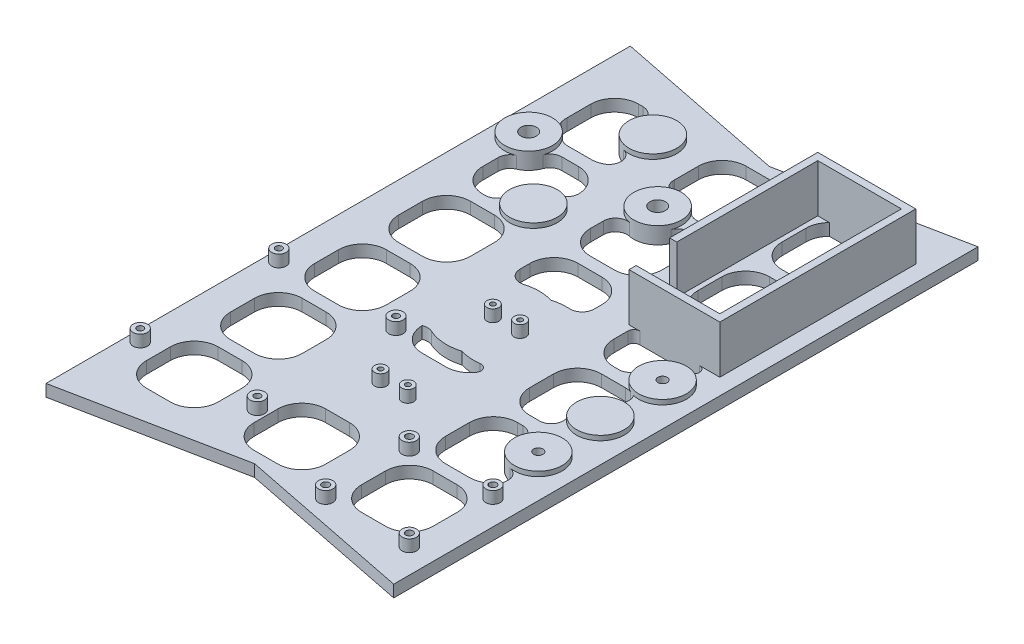
SolidWorks part; units mm, degrees
material "ABS"
ref_plane "Front Plane" through (0, 0, 0) normal (0, 0, 1) x (1, 0, 0)
ref_plane "Top Plane" through (0, 0, 0) normal (0, 1, 0) x (1, 0, 0)
ref_plane "Right Plane" through (0, 0, 0) normal (1, 0, 0) x (0, 0, -1)
ref_axis "X" through (-88.99, 0, 0) along (1, 0, 0)
ref_axis "Y" through (0, 55, 0) along (0, -1, 0)
ref_axis "Z" through (0, 0, -88.99) along (0, 0, 1)
sketch "Sketch1" plane through (0, 0, 0) normal (0, 1, 0) x (1, 0, 0)
  line L0 (-75, 125) -> (0, 110) construction
  line L1 (-75, 125) -> (75, 125) construction
  line L2 (-75, 125) -> (-75, -125) construction
  line L3 (-75, -125) -> (75, -125) construction
  line L4 (75, 125) -> (75, -125) construction
  line L5 (-75, 125) -> (75, -125) construction
  line L6 (-75, -125) -> (75, 125) construction
  line L7 (0, 110) -> (75, 125) construction
  line L8 (-75, 0) -> (75, 0) construction
  line L9 (-75, -125) -> (0, -110) construction
  line L10 (0, -110) -> (75, -125) construction
  line L11 (-73, 122.5604) -> (-73, -122.5604)
  line L12 (-73, -122.5604) -> (0, -107.9604)
  line L13 (0, -107.9604) -> (73, -122.5604)
  line L14 (73, 122.5604) -> (73, -122.5604)
  line L15 (0, 107.9604) -> (73, 122.5604)
  line L16 (-73, 122.5604) -> (0, 107.9604)
  point P0 (0, 0)
  dimension "D1" = 250
  dimension "D2" = 150
  dimension "D3" = 15
  dimension "D4" = 2
extrude "Boss-Extrude1" add sketch "Sketch1" along normal blind 5
sketch "Sketch2" plane through (0, 5, 0) normal (0, 1, 0) x (1, 0, 0)
  line L0 (-73, 122.5604) -> (-73, -122.5604) construction
  line L1 (-50, -102.9604) -> (-40, -102.9604)
  line L2 (-60, -92.9604) -> (-60, -82.9604)
  line L3 (-50, -72.9604) -> (-40, -72.9604)
  line L4 (-30, -92.9604) -> (-30, -82.9604)
  line L5 (-15, -92.9604) -> (-15, -82.9604)
  line L6 (-5, -102.9604) -> (5, -102.9604)
  line L7 (15, -92.9604) -> (15, -82.9604)
  line L8 (-5, -72.9604) -> (5, -72.9604)
  line L9 (30, -92.9604) -> (30, -82.9604)
  line L10 (40, -102.9604) -> (50, -102.9604)
  line L11 (60, -92.9604) -> (60, -82.9604)
  line L12 (40, -72.9604) -> (50, -72.9604)
  line L73 (-60, -57.7762) -> (-60, -47.7762)
  line L74 (-50, -67.7762) -> (-40, -67.7762)
  line L75 (-30, -57.7762) -> (-30, -47.7762)
  line L76 (-50, -37.7762) -> (-40, -37.7762)
  line L77 (-15, -57.7762) -> (-15, -47.7762)
  line L78 (-5, -37.7762) -> (5, -37.7762)
  line L79 (15, -57.7762) -> (15, -47.7762)
  line L80 (-5, -67.7762) -> (5, -67.7762)
  line L81 (30, -57.7762) -> (30, -47.7762)
  line L82 (40, -37.7762) -> (50, -37.7762)
  line L83 (60, -57.7762) -> (60, -47.7762)
  line L84 (40, -67.7762) -> (50, -67.7762)
  line L85 (-60, -22.5921) -> (-60, -12.5921)
  line L86 (-50, -32.5921) -> (-40, -32.5921)
  line L87 (-30, -22.5921) -> (-30, -12.5921)
  line L88 (-50, -2.5921) -> (-40, -2.5921)
  line L89 (-15, -22.5921) -> (-15, -12.5921)
  line L90 (-5, -2.5921) -> (5, -2.5921)
  line L91 (15, -22.5921) -> (15, -12.5921)
  line L92 (-5, -32.5921) -> (5, -32.5921)
  line L93 (30, -22.5921) -> (30, -12.5921)
  line L94 (40, -2.5921) -> (50, -2.5921)
  line L95 (60, -22.5921) -> (60, -12.5921)
  line L96 (40, -32.5921) -> (50, -32.5921)
  line L97 (-60, 12.5921) -> (-60, 22.5921)
  line L98 (-50, 2.5921) -> (-40, 2.5921)
  line L99 (-30, 12.5921) -> (-30, 22.5921)
  line L100 (-50, 32.5921) -> (-40, 32.5921)
  line L101 (-15, 12.5921) -> (-15, 22.5921)
  line L102 (-5, 32.5921) -> (5, 32.5921)
  line L103 (15, 12.5921) -> (15, 22.5921)
  line L104 (-5, 2.5921) -> (5, 2.5921)
  line L105 (30, 12.5921) -> (30, 22.5921)
  line L106 (40, 32.5921) -> (50, 32.5921)
  line L107 (60, 12.5921) -> (60, 22.5921)
  line L108 (40, 2.5921) -> (50, 2.5921)
  line L109 (-60, 47.7762) -> (-60, 57.7762)
  line L110 (-50, 37.7762) -> (-40, 37.7762)
  line L111 (-30, 47.7762) -> (-30, 57.7762)
  line L112 (-50, 67.7762) -> (-40, 67.7762)
  line L113 (-15, 47.7762) -> (-15, 57.7762)
  line L114 (-5, 67.7762) -> (5, 67.7762)
  line L115 (15, 47.7762) -> (15, 57.7762)
  line L116 (-5, 37.7762) -> (5, 37.7762)
  line L117 (30, 47.7762) -> (30, 57.7762)
  line L118 (40, 67.7762) -> (50, 67.7762)
  line L119 (60, 47.7762) -> (60, 57.7762)
  line L120 (40, 37.7762) -> (50, 37.7762)
  line L121 (-60, 82.9604) -> (-60, 92.9604)
  line L122 (-50, 72.9604) -> (-40, 72.9604)
  line L123 (-30, 82.9604) -> (-30, 92.9604)
  line L124 (-50, 102.9604) -> (-40, 102.9604)
  line L125 (-15, 82.9604) -> (-15, 92.9604)
  line L126 (-5, 102.9604) -> (5, 102.9604)
  line L127 (15, 82.9604) -> (15, 92.9604)
  line L128 (-5, 72.9604) -> (5, 72.9604)
  line L129 (30, 82.9604) -> (30, 92.9604)
  line L130 (40, 102.9604) -> (50, 102.9604)
  line L131 (60, 82.9604) -> (60, 92.9604)
  line L132 (40, 72.9604) -> (50, 72.9604)
  arc A0 (-60, -92.9604) -> (-50, -102.9604) centre (-50, -92.9604) ccw
  arc A1 (-40, -102.9604) -> (-30, -92.9604) centre (-40, -92.9604) ccw
  arc A2 (-30, -82.9604) -> (-40, -72.9604) centre (-40, -82.9604) ccw
  arc A3 (-50, -72.9604) -> (-60, -82.9604) centre (-50, -82.9604) ccw
  arc A4 (60, -82.9604) -> (50, -72.9604) centre (50, -82.9604) ccw
  arc A5 (50, -102.9604) -> (60, -92.9604) centre (50, -92.9604) ccw
  arc A6 (40, -102.9604) -> (30, -92.9604) centre (40, -92.9604) cw
  arc A7 (30, -82.9604) -> (40, -72.9604) centre (40, -82.9604) cw
  arc A8 (-15, -82.9604) -> (-5, -72.9604) centre (-5, -82.9604) cw
  arc A9 (-15, -92.9604) -> (-5, -102.9604) centre (-5, -92.9604) ccw
  arc A10 (15, -92.9604) -> (5, -102.9604) centre (5, -92.9604) cw
  arc A11 (15, -82.9604) -> (5, -72.9604) centre (5, -82.9604) ccw
  arc A12 (-50, -37.7762) -> (-60, -47.7762) centre (-50, -47.7762) ccw
  arc A13 (-60, -57.7762) -> (-50, -67.7762) centre (-50, -57.7762) ccw
  arc A14 (-40, -67.7762) -> (-30, -57.7762) centre (-40, -57.7762) ccw
  arc A15 (-30, -47.7762) -> (-40, -37.7762) centre (-40, -47.7762) ccw
  arc A16 (-15, -57.7762) -> (-5, -67.7762) centre (-5, -57.7762) ccw
  arc A17 (-15, -47.7762) -> (-5, -37.7762) centre (-5, -47.7762) cw
  arc A18 (15, -47.7762) -> (5, -37.7762) centre (5, -47.7762) ccw
  arc A19 (15, -57.7762) -> (5, -67.7762) centre (5, -57.7762) cw
  arc A20 (30, -47.7762) -> (40, -37.7762) centre (40, -47.7762) cw
  arc A21 (40, -67.7762) -> (30, -57.7762) centre (40, -57.7762) cw
  arc A22 (60, -47.7762) -> (50, -37.7762) centre (50, -47.7762) ccw
  arc A23 (50, -67.7762) -> (60, -57.7762) centre (50, -57.7762) ccw
  arc A24 (-50, -2.5921) -> (-60, -12.5921) centre (-50, -12.5921) ccw
  arc A25 (-60, -22.5921) -> (-50, -32.5921) centre (-50, -22.5921) ccw
  arc A26 (-40, -32.5921) -> (-30, -22.5921) centre (-40, -22.5921) ccw
  arc A27 (-30, -12.5921) -> (-40, -2.5921) centre (-40, -12.5921) ccw
  arc A28 (-15, -22.5921) -> (-5, -32.5921) centre (-5, -22.5921) ccw
  arc A29 (-15, -12.5921) -> (-5, -2.5921) centre (-5, -12.5921) cw
  arc A30 (15, -12.5921) -> (5, -2.5921) centre (5, -12.5921) ccw
  arc A31 (15, -22.5921) -> (5, -32.5921) centre (5, -22.5921) cw
  arc A32 (30, -12.5921) -> (40, -2.5921) centre (40, -12.5921) cw
  arc A33 (40, -32.5921) -> (30, -22.5921) centre (40, -22.5921) cw
  arc A34 (60, -12.5921) -> (50, -2.5921) centre (50, -12.5921) ccw
  arc A35 (50, -32.5921) -> (60, -22.5921) centre (50, -22.5921) ccw
  arc A36 (-50, 32.5921) -> (-60, 22.5921) centre (-50, 22.5921) ccw
  arc A37 (-60, 12.5921) -> (-50, 2.5921) centre (-50, 12.5921) ccw
  arc A38 (-40, 2.5921) -> (-30, 12.5921) centre (-40, 12.5921) ccw
  arc A39 (-30, 22.5921) -> (-40, 32.5921) centre (-40, 22.5921) ccw
  arc A40 (-15, 12.5921) -> (-5, 2.5921) centre (-5, 12.5921) ccw
  arc A41 (-15, 22.5921) -> (-5, 32.5921) centre (-5, 22.5921) cw
  arc A42 (15, 22.5921) -> (5, 32.5921) centre (5, 22.5921) ccw
  arc A43 (15, 12.5921) -> (5, 2.5921) centre (5, 12.5921) cw
  arc A44 (30, 22.5921) -> (40, 32.5921) centre (40, 22.5921) cw
  arc A45 (40, 2.5921) -> (30, 12.5921) centre (40, 12.5921) cw
  arc A46 (60, 22.5921) -> (50, 32.5921) centre (50, 22.5921) ccw
  arc A47 (50, 2.5921) -> (60, 12.5921) centre (50, 12.5921) ccw
  arc A48 (-50, 67.7762) -> (-60, 57.7762) centre (-50, 57.7762) ccw
  arc A49 (-60, 47.7762) -> (-50, 37.7762) centre (-50, 47.7762) ccw
  arc A50 (-40, 37.7762) -> (-30, 47.7762) centre (-40, 47.7762) ccw
  arc A51 (-30, 57.7762) -> (-40, 67.7762) centre (-40, 57.7762) ccw
  arc A52 (-15, 47.7762) -> (-5, 37.7762) centre (-5, 47.7762) ccw
  arc A53 (-15, 57.7762) -> (-5, 67.7762) centre (-5, 57.7762) cw
  arc A54 (15, 57.7762) -> (5, 67.7762) centre (5, 57.7762) ccw
  arc A55 (15, 47.7762) -> (5, 37.7762) centre (5, 47.7762) cw
  arc A56 (30, 57.7762) -> (40, 67.7762) centre (40, 57.7762) cw
  arc A57 (40, 37.7762) -> (30, 47.7762) centre (40, 47.7762) cw
  arc A58 (60, 57.7762) -> (50, 67.7762) centre (50, 57.7762) ccw
  arc A59 (50, 37.7762) -> (60, 47.7762) centre (50, 47.7762) ccw
  arc A60 (-50, 102.9604) -> (-60, 92.9604) centre (-50, 92.9604) ccw
  arc A61 (-60, 82.9604) -> (-50, 72.9604) centre (-50, 82.9604) ccw
  arc A62 (-40, 72.9604) -> (-30, 82.9604) centre (-40, 82.9604) ccw
  arc A63 (-30, 92.9604) -> (-40, 102.9604) centre (-40, 92.9604) ccw
  arc A64 (-15, 82.9604) -> (-5, 72.9604) centre (-5, 82.9604) ccw
  arc A65 (-15, 92.9604) -> (-5, 102.9604) centre (-5, 92.9604) cw
  arc A66 (15, 92.9604) -> (5, 102.9604) centre (5, 92.9604) ccw
  arc A67 (15, 82.9604) -> (5, 72.9604) centre (5, 82.9604) cw
  arc A68 (30, 92.9604) -> (40, 102.9604) centre (40, 92.9604) cw
  arc A69 (40, 72.9604) -> (30, 82.9604) centre (40, 82.9604) cw
  arc A70 (60, 92.9604) -> (50, 102.9604) centre (50, 92.9604) ccw
  arc A71 (50, 72.9604) -> (60, 82.9604) centre (50, 82.9604) ccw
  point P81 (-30, -102.9604)
  point P84 (-30, -72.9604)
  point P87 (-60, -72.9604)
  dimension "D9" = 10
  dimension "D7" = 10
  dimension "D1" = 30
  dimension "D2" = 30
  dimension "D3" = 13
  dimension "D4" = 5
  dimension "D6" = 15
  dimension "D8" = 6
  dimension "D10" = 5
  dimension "D5" = 3
extrude "Cut-Extrude1" cut sketch "Sketch2" against normal through all
sketch "Sketch3" plane through (0, 5, 0) normal (0, 1, 0) x (1, 0, 0)
  line L1 (-73, 122.5604) -> (-73, -122.5604) construction
  circle A0 centre (-68, -29.5604) radius 3
  circle A1 centre (-19, -29.5604) radius 3
  circle A2 centre (-68, -87.5604) radius 3
  circle A3 centre (-19, -87.5604) radius 3
  dimension "D1" = 6
  dimension "D2" = 49
  dimension "D3" = 58
  dimension "D4" = 5
  dimension "D5" = 35
extrude "Boss-Extrude2" add sketch "Sketch3" along normal blind 5 and the other way through all
sketch "Sketch4" plane through (0, 10, 0) normal (0, 1, 0) x (1, 0, 0)
  circle A1 centre (-19, -87.5604) radius 1.35
  circle A2 centre (-68, -87.5604) radius 1.35
  circle A3 centre (-68, -29.5604) radius 1.35
  circle A4 centre (-19, -29.5604) radius 1.35
  dimension "D1" = 2.7
extrude "Cut-Extrude2" cut sketch "Sketch4" against normal through all
sketch "Sketch5" plane through (0, 5, 0) normal (0, 1, 0) x (1, 0, 0)
  line L0 (30, -87.9604) -> (60, -87.9604) construction
  line L1 (30, -82.9604) -> (30, -92.9604) construction
  line L2 (60, -92.9604) -> (60, -82.9604) construction
  circle A0 centre (27.5, -70.4604) radius 3
  circle A2 centre (62.5, -70.4604) radius 3
  circle A4 centre (62.5, -105.4604) radius 3
  circle A6 centre (27.5, -105.4604) radius 3
  circle A9 centre (45, -87.9604) radius 24.7487 construction
  dimension "D2" = 6
  dimension "D3" = 35
  dimension "D4" = 35
extrude "Boss-Extrude3" add sketch "Sketch5" along normal blind 5
sketch "Sketch6" plane through (0, 10, 0) normal (0, 1, 0) x (1, 0, 0)
  circle A0 centre (27.5, -70.4604) radius 1.5
  circle A1 centre (62.5, -70.4604) radius 1.5
  circle A2 centre (62.5, -105.4604) radius 1.5
  circle A3 centre (27.5, -105.4604) radius 1.5
  dimension "D1" = 3
extrude "Cut-Extrude3" cut sketch "Sketch6" against normal through all
sketch "Sketch7" plane through (0, 5, 0) normal (0, 1, 0) x (1, 0, 0)
  line L0 (73, -122.5604) -> (73, 122.5604) construction
  line L3 (57, 6) -> (57, -46) construction
  circle A0 centre (57, -46) radius 10
  circle A1 centre (57, 6) radius 10
  circle A2 centre (57, -20) radius 10
  dimension "D1" = 20
  dimension "D2" = 16
  dimension "D3" = 52
  dimension "D4" = 20
extrude "Boss-Extrude4" add sketch "Sketch7" along normal blind 2 and the other way through all
sketch "Sketch8" plane through (0, 7, 0) normal (0, 1, 0) x (1, 0, 0)
  circle A0 centre (57, 6) radius 1.95
  circle A1 centre (57, -46) radius 1.95
  dimension "D1" = 3.9
extrude "Cut-Extrude4" cut sketch "Sketch8" against normal through all
sketch "Sketch9" plane through (0, 5, 0) normal (0, 1, 0) x (1, 0, 0)
  line L0 (-73, 0) -> (73, 0) construction
  line L2 (-73, 122.5604) -> (-73, -122.5604) construction
  line L3 (73, -122.5604) -> (73, 122.5604) construction
  circle A0 centre (-3, -5) radius 2.5
  circle A1 centre (-3, -52) radius 2.5
  circle A2 centre (8.4, -52) radius 2.5
  circle A3 centre (8.4, -5) radius 2.5
  dimension "D1" = 5
  dimension "D4" = 70
  dimension "D2" = 11.4
  dimension "D3" = 47
  dimension "D5" = 5
extrude "Boss-Extrude5" add sketch "Sketch9" along normal blind 5
sketch "Sketch16" plane through (0, 5, 0) normal (0, -1, 0) x (1, 0, 0)
  line L0 (-5, 32.5921) -> (5, 32.5921) construction
  line L1 (-93.8107, 28.5) -> (150.737, 28.5) construction
  line L4 (-3, 52) -> (-3, 5) construction
  circle A0 centre (8.4, 52) radius 19.4079
  circle A1 centre (-3, 52) radius 19.4079
  circle A4 centre (-3, 52) radius 2.5 construction
  circle A5 centre (-3, 5) radius 2.5 construction
  circle A6 centre (-3, 52) radius 2.5 construction
  circle A7 centre (-3, 5) radius 2.5 construction
  circle A8 centre (8.4, 5) radius 19.4079
  circle A9 centre (-3, 5) radius 19.4079
  point P20 (-3, 28.5)
  circle M3 centre (8.4, 52) radius 2.5
extrude "Boss-Extrude10" add sketch "Sketch16" along normal up to surface (5 mm away) contours A0 A1 | A0 A1 M3 | M3 | A1 A0 | A9 | A8 region at (18.1683, 5, 52) region at (2.5462, 5, 52) region at (-12.7683, 5, 52) region at (8.4, 5, 52) up to face at (57, 0, -4.05)
sketch "Sketch10" plane through (0, 10, 0) normal (0, 1, 0) x (1, 0, 0)
  circle A0 centre (8.4, -5) radius 1.05
  circle A1 centre (8.4, -52) radius 1.05
  circle A2 centre (-3, -52) radius 1.05
  circle A3 centre (-3, -5) radius 1.05
  dimension "D1" = 2.1
extrude "Cut-Extrude5" cut sketch "Sketch10" against normal through all
sketch "Sketch11" plane through (0, 5, 0) normal (0, 1, 0) x (1, 0, 0)
  line L0 (-73, 122.5604) -> (-73, -122.5604) construction
  line L1 (-34, 92.9604) -> (-34, 42.9604) construction
  line L2 (-61, 67.9604) -> (-7, 67.9604) construction
  circle A3 centre (-7, 67.9604) radius 10
  circle A4 centre (-61, 67.9604) radius 10
  circle A5 centre (-34, 92.9604) radius 10
  circle A6 centre (-34, 42.9604) radius 10
  point P11 (-34, 67.9604)
  dimension "D1" = 20
  dimension "D2" = 54
  dimension "D3" = 40
  dimension "D4" = 12
  dimension "D5" = 50
extrude "Boss-Extrude6" add sketch "Sketch11" along normal blind 2 and the other way through all
sketch "Sketch12" plane through (0, 7, 0) normal (0, 1, 0) x (1, 0, 0)
  circle A0 centre (-61, 67.9604) radius 3.25
  circle A1 centre (-7, 67.9604) radius 3.25
  dimension "D1" = 6.5
extrude "Cut-Extrude6" cut sketch "Sketch12" against normal through all
sketch "Sketch13" plane through (0, 5, 0) normal (0, 1, 0) x (1, 0, 0)
  line L0 (28, 20.9604) -> (66, 20.9604)
  line L1 (66, 20.9604) -> (66, 102.9604)
  line L2 (66, 102.9604) -> (25, 102.9604)
  line L3 (25, 102.9604) -> (25, 40.9604)
  line L4 (25, 40.9604) -> (28, 40.9604)
  line L5 (28, 40.9604) -> (28, 99.9604)
  line L6 (28, 99.9604) -> (63, 99.9604)
  line L7 (63, 99.9604) -> (63, 23.9604)
  line L8 (63, 23.9604) -> (28, 23.9604)
  line L9 (28, 23.9604) -> (28, 20.9604)
  line L10 (73, -122.5604) -> (73, 122.5604) construction
  line L11 (50, 102.9604) -> (40, 102.9604) construction
  dimension "D1" = 62
  dimension "D2" = 3
  dimension "D3" = 3
  dimension "D4" = 3
  dimension "D5" = 3
  dimension "D6" = 35
  dimension "D7" = 76
  dimension "D9" = 7
extrude "Boss-Extrude7" add sketch "Sketch13" along normal blind 20 and the other way through all
fillet "Fillet2" radius 5 20 edges at (47.5986, 2.5, -2.5921) (51.2064, 2.5, 37.8493) (56.7216, 2.5, 29.9961) (59.7538, 2.5, 10.3866) (-30, 2.5, -52.1255) (-12.481, 2.5, -76.3245) (1.6603, 2.5, -72.9604) (-58.4629, 2.5, -77.6332) (-52.5371, 2.5, -73.2876) (-30, 2.5, -83.7952) (-37, 2.5, -102.4998) (2.9983, 2.5, -67.7762) (-14.3879, 2.5, -61.2211) (-42.5513, 2.5, -37.7762) (-59.9972, 2.5, -58.0108) (-51.0028, 2.5, -67.7258) (60, 2.5, 55.5394) (-14.7647, 2.5, -10.4356) (15, 2.5, -13.2512) (-15, 2.5, 20.2534)
fillet "Fillet3" radius 2.5 6 edges at (14.9777, 2.5, 23.2593) (60, 2.5, -15.5394) (30.0941, 2.5, -23.9604) (59.9059, 2.5, -23.9604) (30, 2.5, -20.9604) (60, 2.5, -20.9604)
sketch "Sketch19" plane through (0, 0, 0) normal (0, -1, 0) x (1, 0, 0)
  line L6 (-72.75, -122.2554) -> (0, -107.7054)
  line L7 (0, -107.7054) -> (72.75, -122.2554)
  line L8 (72.75, -122.2554) -> (72.75, 122.2554)
  line L9 (72.75, 122.2554) -> (0, 107.7054)
  line L10 (0, 107.7054) -> (-72.75, 122.2554)
  line L11 (-72.75, 122.2554) -> (-72.75, -122.2554)
  line L12 (-73, -122.5604) -> (0, -107.9604)
  line L13 (0, -107.9604) -> (73, -122.5604)
  line L14 (73, -122.5604) -> (73, 122.5604)
  line L15 (73, 122.5604) -> (0, 107.9604)
  line L16 (0, 107.9604) -> (-73, 122.5604)
  line L17 (-73, 122.5604) -> (-73, -122.5604)
  line L18 (-73, -122.5604) -> (0, -107.9604)
  line L19 (0, -107.9604) -> (73, -122.5604)
  line L20 (73, -122.5604) -> (73, 122.5604)
  line L21 (73, 122.5604) -> (0, 107.9604)
  line L22 (0, 107.9604) -> (-73, 122.5604)
  line L23 (-73, 122.5604) -> (-73, -122.5604)
  dimension "D1" = 0
  dimension "D2" = 0.25
extrude "Cut-Extrude8" cut sketch "Sketch19" against normal through all
